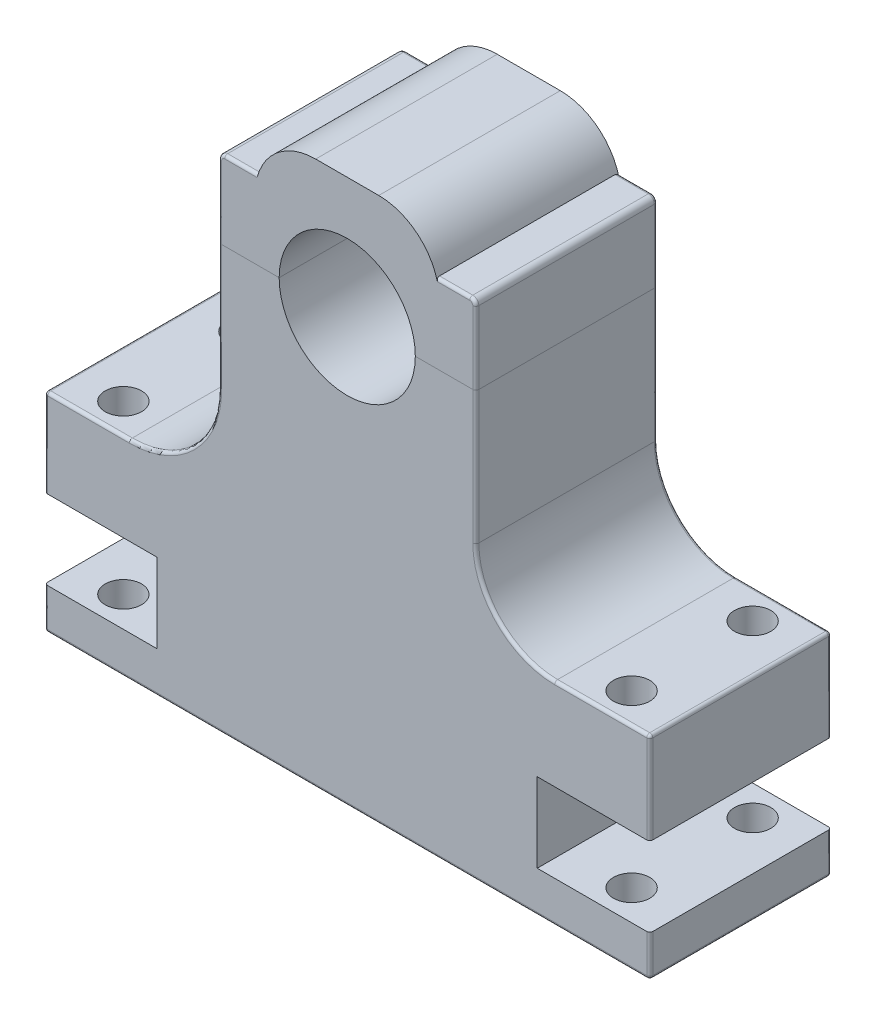
SolidWorks part; units mm, degrees
ref_plane "Plan de face" through (0, 0, 0) normal (0, 0, 1) x (1, 0, 0)
ref_plane "Plan de dessus" through (0, 0, 0) normal (0, 1, 0) x (1, 0, 0)
ref_plane "Plan de droite" through (0, 0, 0) normal (1, 0, 0) x (0, 0, -1)
sketch "Esquisse1" plane through (0, 0, 0) normal (0, 0, 1) x (1, 0, 0)
  line L0 (0, 0) -> (1000, 0)
  line L1 (1000, 0) -> (1000, 150)
  line L3 (0, 144.3329) -> (0, 0)
  line L4 (287.5, 374.9177) -> (287.5, 630)
  line L5 (352.5, 700) -> (647.5, 700)
  line L6 (712.5, 630) -> (712.5, 375)
  line L7 (0, 144.3329) -> (139.9789, 144.3329)
  line L8 (287.5, 291.854) -> (287.5, 374.9177)
  line L9 (1000, 150) -> (842.778, 150)
  line L10 (712.5, 375) -> (712.5, 280.278)
  line L11 (647.5, 700) -> (647.5, 630)
  line L12 (647.5, 630) -> (712.5, 630)
  line L13 (500, 500) -> (500, 0) construction
  line L16 (287.5, 630) -> (352.5, 630)
  line L17 (352.5, 700) -> (352.5, 630)
  circle A2 centre (500, 500) radius 112.5
  arc A3 (139.9789, 144.3329) -> (287.5, 291.854) centre (139.9789, 291.854) ccw
  arc A4 (842.778, 150) -> (712.5, 280.278) centre (842.778, 280.278) cw
  point P6 (320, 630)
  dimension "D1" = 225
  dimension "D2" = 500
  dimension "D3" = 65
  dimension "D4" = 700
  dimension "D5" = 65
  dimension "D6" = 287.5
  dimension "D7" = 1000
  dimension "D8" = 287.5
  dimension "D9" = 70
  dimension "D10" = 70
extrude "Boss.-Extru.1" add sketch "Esquisse1" against normal blind 300
sketch "Esquisse2" plane through (0, 144.3329, 0) normal (0, 1, 0) x (1, 0, 0)
  line L0 (139.9789, 300) -> (0, 300) construction
  line L1 (139.9789, 0) -> (0, 0) construction
  line L2 (0, 300) -> (0, 0) construction
  circle A0 centre (80, 250) radius 30
  circle A1 centre (80, 50) radius 30
  dimension "D1" = 60
  dimension "D2" = 60
  dimension "D3" = 50
  dimension "D4" = 50
  dimension "D5" = 80
  dimension "D6" = 80
extrude "Enlèv. mat.-Extru.1" cut sketch "Esquisse2" against normal blind 500
fillet "Congé3" radius 100 2 edges at (352.5, 700, -150) (647.5, 700, -150)
fillet "Congé4" radius 10 2 edges at (287.5, 630, -150) (712.5, 630, -150)
sketch "Esquisse3" plane through (0, 150, 0) normal (0, 1, 0) x (1, 0, 0)
  line L0 (1000, 300) -> (842.778, 300) construction
  line L1 (1000, 0) -> (842.778, 0) construction
  line L2 (1000, 300) -> (1000, 0) construction
  circle A0 centre (920, 250) radius 30
  circle A1 centre (920, 50) radius 30
  dimension "D1" = 60
  dimension "D2" = 60
  dimension "D3" = 50
  dimension "D4" = 50
  dimension "D5" = 80
  dimension "D6" = 80
extrude "Enlèv. mat.-Extru.2" cut sketch "Esquisse3" against normal through all
sketch "Esquisse6" plane through (0, 0, 0) normal (0, 0, 1) x (1, 0, 0)
  line L0 (0, 0) -> (0, -200)
  line L1 (0, -200) -> (1000, -200)
  line L2 (1000, -200) -> (1000, 0)
  line L3 (0, 0) -> (1000, 0) construction
  line L4 (0, 0) -> (1000, 0)
  point P0 (1000, -200)
  dimension "D1" = 200
extrude "Boss.-Extru.2" add sketch "Esquisse6" against normal blind 300
sketch "Esquisse7" plane through (0, 0, 0) normal (0, 1, 0) x (1, 0, 0)
  circle A0 centre (80.6625, 253.0556) radius 33.1266
  circle A1 centre (80, 50) radius 30
  circle A3 centre (920, 250) radius 30
  circle A4 centre (920, 50) radius 30 construction
  circle A5 centre (920, 50) radius 30
extrude "Enlèv. mat.-Extru.4" cut sketch "Esquisse7" against normal blind 300
ref_plane "Plan2" through (500, 0, 0) normal (1, 0, 0) x (0, 0, -1)
sketch "Esquisse11" plane through (0, 630, 0) normal (0, 1, 0) x (1, 0, 0)
  line L0 (352.5, 300) -> (297.5, 300) construction
  line L1 (500, -165) -> (500, 165) construction
  circle A0 centre (325, 260) radius 20
  circle A1 centre (675, 260) radius 20
  circle A2 centre (325, 60) radius 20
  circle A3 centre (675, 60) radius 20
  dimension "D1" = 40
  dimension "D2" = 40
  dimension "D3" = 2
fillet "Congé6" radius 5 30 edges at (921.389, 150, 0) (675, 630, 0) (709.5711, 627.0711, 0) (712.5, 450.139, 0) (921.389, 150, -300) (675, 630, -300) (709.5711, 627.0711, -300) (712.5, 450.139, -300) (325, 630, -300) (290.4289, 627.0711, -300) (287.5, 455.927, -300) (244.2921, 187.5409, -300) (325, 630, 0) (290.4289, 627.0711, 0) (69.9895, 144.3329, 0) (244.2921, 187.5409, 0) (1000, -200, -150) (500, -200, -300) (0, -200, -150) (500, -200, 0) (750.6576, 188.1576, 0) (1000, 150, -150) (1000, -25, 0) (1000, -25, -300) (750.6576, 188.1576, -300) (69.9895, 144.3329, -300) (0, -27.8335, -300) (0, 144.3329, -150) (0, -27.8335, 0) (287.5, 455.927, 0)
ref_plane "Plan1" through (0, 500, 0) normal (0, -1, 0) x (-1, 0, 0)
split "Fractionner1" trim tools "Plan1" bodies to split 107 resulting bodies 108 109
sketch "Esquisse12" plane through (0, 0, -300) normal (0, 0, -1) x (-1, 0, 0)
  line L0 (0, 139.3329) -> (0, -195) construction
  line L1 (-186, -1) -> (264.7288, -1)
  line L2 (-186, -1) -> (-186, -132)
  line L3 (-186, -132) -> (264.7288, -132)
  line L4 (264.7288, -1) -> (264.7288, -132)
  line L5 (39.3644, -132) -> (39.3644, -1) construction
  line L6 (-186, -66.5) -> (264.7288, -66.5) construction
  line L7 (-995, -195) -> (-5, -195) construction
  line L8 (-500, 165) -> (-500, -165) construction
  line L9 (-814, -132) -> (-1264.7288, -132)
  line L10 (-1264.7288, -1) -> (-1264.7288, -132)
  line L11 (-814, -1) -> (-1264.7288, -1)
  line L12 (-814, -1) -> (-814, -132)
  point P72 (39.3644, -66.5)
  dimension "D1" = 186
  dimension "D2" = 131
  dimension "D3" = 63
extrude "Enlèv. mat.-Extru.5" cut sketch "Esquisse12" against normal through all
